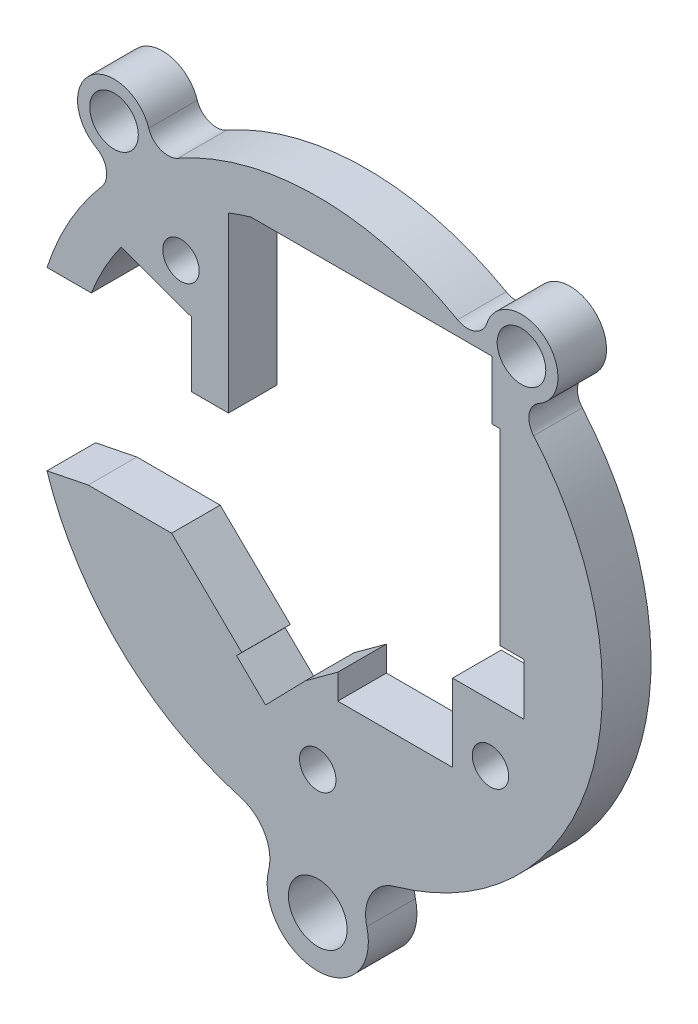
SolidWorks part; units mm, degrees
ref_plane "Front Plane" through (0, 0, 0) normal (0, 0, 1) x (1, 0, 0)
ref_plane "Top Plane" through (0, 0, 0) normal (0, 1, 0) x (1, 0, 0)
ref_plane "Right Plane" through (0, 0, 0) normal (1, 0, 0) x (0, 0, -1)
sketch "Sketch1" plane through (0, 0, 0) normal (0, 0, 1) x (1, 0, 0)
  line L1 (-14.9521, -2.9485) -> (-16.9841, -2.9485)
  line L2 (-16.9841, 2.9485) -> (-16.9841, 5.5245)
  line L3 (-14.9521, 2.9485) -> (-16.9841, 2.9485)
  line L4 (-16.9841, 5.5245) -> (-21.1739, 5.5245)
  line L5 (-16.9841, -2.9485) -> (-16.9841, -5.5245)
  line L6 (-16.9841, -5.5245) -> (-20.8712, -5.5245)
  line L7 (-15.24, 0) -> (-21.59, 0) construction
  line B0 (-15.24, 18.2372) -> (15.24, 18.2372)
  line B1 (11.43, 14.6558) -> (11.43, -0.8128)
  line B2 (0, 18.2372) -> (0, 0) construction
  line B3 (-5.6007, 14.1736) -> (-5.6007, -0.8128)
  line B4 (11.43, 14.6558) -> (-4.1791, 14.6558)
  line B5 (-5.6007, -0.8128) -> (11.43, -0.8128)
  line B6 (8.4582, -4.064) -> (12.9413, -4.064)
  line B7 (11.43, -0.8128) -> (12.9413, -0.8128)
  line B8 (12.9413, -0.8128) -> (12.9413, -4.064)
  line B9 (8.4582, -7.3406) -> (1.2573, -7.3406)
  line B10 (8.4582, -4.064) -> (8.4582, -7.3406)
  line B11 (-4.3942, -0.8128) -> (-4.3942, -4.064)
  line B12 (-4.3942, -4.064) -> (1.2573, -4.064)
  line B13 (1.2573, -4.064) -> (1.2573, -7.3406)
  line B14 (-0.7747, -8.8265) -> (-3.2737, -11.3919)
  line B15 (-0.7747, -8.8265) -> (-2.5941, -7.0541)
  line B16 (-2.5941, -7.0541) -> (-2.9176, -7.3862)
  line B17 (-2.9176, -7.3862) -> (-8.5123, -1.9362)
  line B18 (-8.5123, -1.9362) -> (-10.3645, -3.8375)
  line B19 (-10.3645, -3.8375) -> (-4.7697, -9.2875)
  line B20 (-4.7697, -9.2875) -> (-5.0932, -9.6195)
  line B21 (-5.0932, -9.6195) -> (-3.2737, -11.3919)
  line B22 (-12.3326, 18.2372) -> (-12.3326, 8.9535)
  line B23 (-7.9248, 18.2372) -> (-7.9248, 7.366) construction
  line B24 (-12.3326, 8.9535) -> (-7.9248, 7.366)
  line B25 (-5.6007, 3.302) -> (-7.9248, 3.302)
  line B26 (-7.9248, 3.302) -> (-7.9248, 7.366)
  line B27 (-14.3951, -5.0038) -> (-9.1672, -5.0038)
  line B28 (-0.7747, -8.8265) -> (1.2573, -7.3406)
  arc B29 (-3.302, 14.878) -> (3.302, 14.878) centre (0, 0) ccw
  circle B30 centre (0, -18.415) radius 1.4224
  circle B31 centre (0, 18.415) radius 1.4224
  circle B32 centre (0, 0) radius 21.59
  line B33 (1.2573, -8.9154) -> (8.4582, -8.9154)
  line B34 (1.2573, -7.3406) -> (1.2573, -8.9154)
  line B35 (8.4582, -7.3406) -> (8.4582, -8.9154)
  dimension "D1" = 2.032
  dimension "D2" = 11.049
sketch_block_instance "Block1-1"
sketch_block "Block1" parameters "D1"=3.81, "D2"=30.48, "D3"=3.5814, "D4"=9.6393, "D5"=19.05, "D6"=22.3012, "D7"=1.5113, "D8"=4.4831, "D9"=6.5278, "D10"=7.2009, "D11"=5.6515, "D12"=27.0637, "D13"=29.6291, "D14"=3.5814, "D15"=14.4653, "D16"=2.54, "D17"=2.6543, "D18"=10.3505, "D19"=9.2837, "D20"=10.8712, "D21"=7.3152, "D22"=14.9352, "D23"=23.241
extrude "Boss-Extrude1" add sketch "Sketch1" along normal blind 3.048 contours B0 B32 B29 B4 B1 B31 B30 | B27 B29 B1 B7 B8 B6 B10 B9 B28 B14 B21 B20 B19 | B3 B29 B24 B26 B25 | B0 B32 B31 | B22 B32 L4 L2 L3 B29 region at (-15.2714, -4.1381, 0) region at (-15.71, 9.7203, 0) region at (-11.7811, -5.3936, 0) region at (-7.7282, 8.9883, 0) region at (0, 21.3565, 0)
sketch "Sketch2" plane through (0, 0, 3.048) normal (0, 0, 1) x (1, 0, 0)
  line L0 (-14.3951, -5.0038) -> (-16.9841, -5.5245)
  line L2 (-16.9841, 5.5245) -> (-14.2034, 5.5245)
  line L3 (-14.3951, -5.0038) -> (-14.2034, 5.5245)
  line L4 (-16.9841, -5.5245) -> (-16.9841, 5.5245)
  arc A0 (-12.3326, 8.9535) -> (-14.9521, 2.9485) centre (0, 0) ccw construction
extrude "Cut-Extrude1" cut sketch "Sketch2" against normal through all
sketch "Sketch3" plane through (0, 0, 3.048) normal (0, 0, 1) x (1, 0, 0)
  line L0 (0, 0) -> (11.43, 14.6558) construction
  line L1 (0, 0) -> (-14.0833, 10.9835) construction
  line L2 (0, 0) -> (-10.9835, -14.0833) construction
  line L3 (0, 0) -> (14.0833, -10.9835) construction
  circle A0 centre (0, 0) radius 17.86
  circle A1 centre (0, 0) radius 21.59
extrude "Cut-Extrude2" cut sketch "Sketch3" against normal through all
sketch "Sketch4" plane through (0, 0, 3.048) normal (0, 0, 1) x (1, 0, 0)
  line L0 (0, -21.035) -> (0, 0) construction
  line L6 (10.2071, 14.6558) -> (11.43, 14.6558)
  line L7 (11.43, 14.6558) -> (11.43, 13.7235)
  line L19 (-21.6223, 17.86) -> (27.8478, 17.86) construction
  circle A0 centre (0, 0) radius 17.86
  circle A1 centre (12.7793, 15.574) radius 1.524
  circle A2 centre (-12.7793, 15.574) radius 2.286
  circle A3 centre (12.7793, 15.574) radius 2.286
  circle A4 centre (-14.5094, 12.4672) radius 1.27
  circle A5 centre (-9.3946, 16.6642) radius 1.27
  circle A6 centre (-12.7793, 15.574) radius 1.524
  circle A7 centre (0, -21.035) radius 1.8415
  circle A8 centre (0, -21.035) radius 3.175
  circle A9 centre (9.3946, 16.6642) radius 1.27
  circle A11 centre (14.5094, 12.4672) radius 1.27
  arc A12 (-1.2889, 17.8134) -> (1.2889, 17.8134) centre (0, 18.415) ccw
  arc A13 (-1.2889, 17.8134) -> (1.2889, 17.8134) centre (0, 18.415) ccw construction
  circle A14 centre (5.5404, -19.6332) radius 2.54
  circle A15 centre (-5.5404, -19.6332) radius 2.54
  arc M3 (-1.2889, -17.8134) -> (1.2889, -17.8134) centre (0, -18.415) cw
  arc M4 (1.2889, -17.8134) -> (11.43, 13.7235) centre (0, 0) ccw
  dimension "D2" = 3.048
  dimension "D4" = 2.54
  dimension "D3" = 3.683
  dimension "D1" = 4.572
  dimension "D5" = 6.35
  dimension "D6" = 5.08
extrude "Boss-Extrude3" add sketch "Sketch4" against normal blind 3.048 contours A5 A2 A0 | A2 A6 | A4 A0 A2 | A0 A12 | A9 A0 L6 A3 | L7 A3 L6 A1 | A11 A3 L7 A0 | A8 A7 | A15 A8 A0 | A14 A0 A8 M4 | A0 M3 region at (10.0871, 15.2114, 3.048) region at (10.5609, 15.4611, 3.048) region at (12.8284, 12.9196, 3.048) region at (0, 17.4932, 3.048) region at (-10.1667, 15.1037, 3.048) region at (2.6103, -18.2487, 3.048) region at (-12.8282, 12.9198, 3.048) region at (-12.5808, 13.3615, 3.048) region at (0, -17.4932, 3.048) region at (3.0615, -20.6537, 3.048) region at (-2.6103, -18.2487, 3.048)
sketch "Sketch7" plane through (0, 0, 3.048) normal (0, 0, 1) x (1, 0, 0)
  line L1 (11.43, 14.6558) -> (10.922, 14.6558)
  line L2 (11.43, 14.6558) -> (11.43, 10.9728)
  line L3 (11.43, 10.9728) -> (10.922, 10.9728)
  line L4 (10.922, 14.6558) -> (10.922, 10.9728)
  dimension "D1" = 0.508
  dimension "D2" = 3.683
extrude "Boss-Extrude4" add sketch "Sketch7" against normal up to vertex (3.048 mm away) up to point (11.43, 14.6558, 0)
sketch "Sketch8" plane through (0, 0, 3.048) normal (0, 0, 1) x (1, 0, 0)
  line L0 (-15.24, 18.2372) -> (15.24, 18.2372) construction
  line L1 (-15.24, 18.2372) -> (15.24, 18.2372)
  line L2 (0, 18.2372) -> (0, -12.1158) construction
  line L3 (10.8325, 18.2372) -> (10.8325, -6.5024) construction
  line L4 (0, 0) -> (14.5917, -10.2986) construction
  line L5 (-8.579, 11.2522) -> (-8.579, 18.2372) construction
  circle A0 centre (0, -13.2588) radius 1.143
  circle A1 centre (10.8325, -7.6454) radius 1.143
  arc A2 (4.8506, -17.1887) -> (13.5462, 11.6395) centre (0, 0) ccw construction
  circle A3 centre (-8.579, 10.1092) radius 1.143
  circle A4 centre (0, 0) radius 15.2591 construction
  circle A5 centre (0, 0) radius 13.2588 construction
  dimension "D2" = 2.286
  dimension "D4" = 6.985
  dimension "D5" = 30.5181
  dimension "D1" = 30.353
  dimension "D3" = 24.7396
extrude "Cut-Extrude3" cut sketch "Sketch8" against normal through all contours A0 | A1 | A3 region at (0, -13.2588, 3.048) region at (10.8325, -7.6454, 3.048) region at (-8.579, 10.1092, 3.048)
